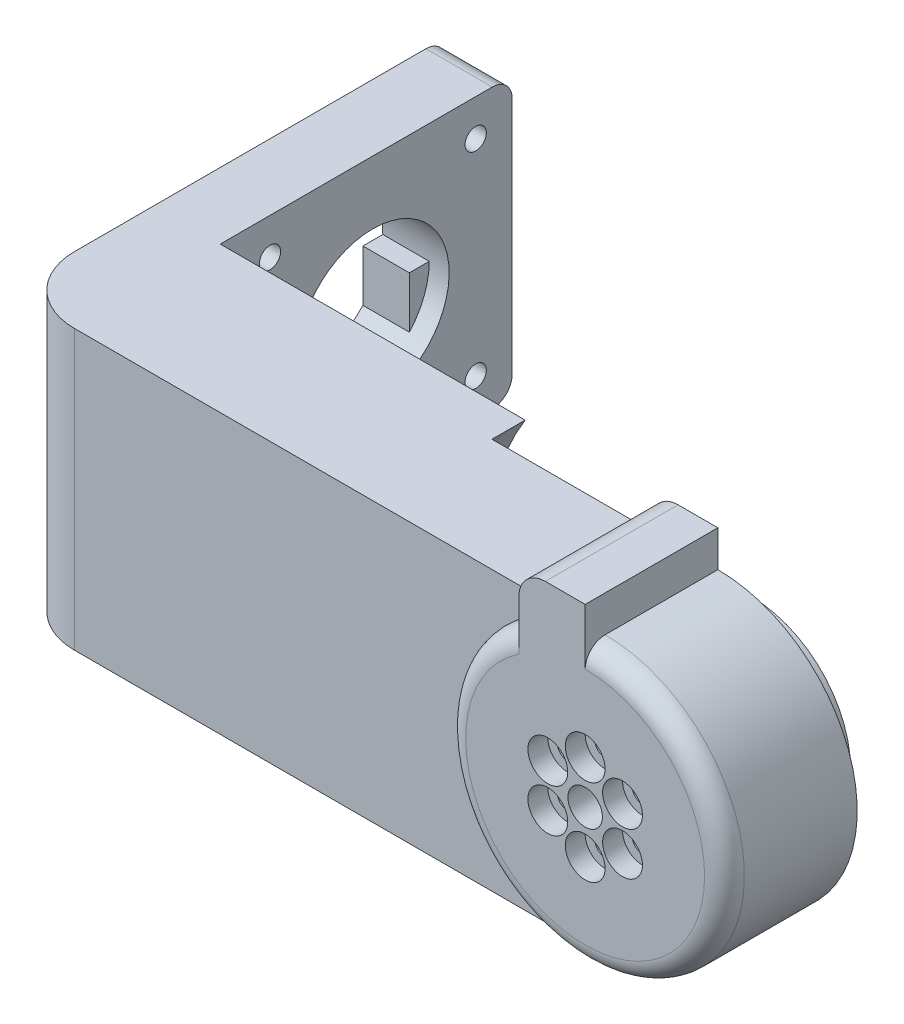
SolidWorks part; units mm, degrees
ref_plane "前视基准面" through (0, 0, 0) normal (0, 0, 1) x (1, 0, 0)
ref_plane "上视基准面" through (0, 0, 0) normal (0, 1, 0) x (1, 0, 0)
ref_plane "右视基准面" through (0, 0, 0) normal (1, 0, 0) x (0, 0, -1)
sketch "草图1" plane through (0, 0, 0) normal (0, 0, 1) x (1, 0, 0)
  line L1 (-45, 21) -> (45, 21)
  line L2 (-45, 21) -> (-45, -21)
  line L3 (-45, -21) -> (45, -21)
  line L4 (45, 21) -> (45, -21)
  line L5 (0, -21) -> (0, 21) construction
  line L6 (-45, 0) -> (45, 0) construction
  point P0 (0, 0)
  dimension "D1" = 90
  dimension "D2" = 42
extrude "凸台-拉伸1" add sketch "草图1" along normal blind 54
sketch "草图2" plane through (0, 0, 0) normal (0, 0, -1) x (-1, 0, 0)
  circle A0 centre (-45, 0) radius 21
  dimension "D1" = 42
extrude "凸台-拉伸2" add sketch "草图2" against normal up to surface (54 mm away) up to face at (0, 0, 54)
sketch "草图3" plane through (0, 0, 0) normal (0, 0, -1) x (-1, 0, 0)
  circle A0 centre (-45, 0) radius 40
  dimension "D1" = 80
extrude "切除-拉伸1" cut sketch "草图3" against normal offset from surface (49 mm away) 5 up to face at (5.25, 0, 54)
sketch "草图4" plane through (0, 0, 49) normal (0, 0, -1) x (-1, 0, 0)
  circle A0 centre (-45, 0) radius 15
  dimension "D1" = 30
extrude "凸台-拉伸3" add sketch "草图4" along normal blind 5
sketch "草图5" plane through (0, 0, 54) normal (0, 0, 1) x (1, 0, 0)
  circle A0 centre (45, 0) radius 21
  dimension "D1" = 42
extrude "凸台-拉伸4" add sketch "草图5" along normal blind 15
sketch "草图7" plane through (0, 0, 69) normal (0, 0, 1) x (1, 0, 0)
  line L0 (0, 0) -> (78.2042, 0) construction
  line L1 (45, 21) -> (45, -21) construction
  circle A0 centre (45, 0) radius 21 construction
  point P8 (45, 0)
sketch "草图10" plane through (0, 0, 0) normal (0, 0, -1) x (-1, 0, 0)
  line L0 (45, -21) -> (-10.9559, -21) construction
  line L1 (-10.9559, 21) -> (35, 21)
  line L2 (-10.9559, 21) -> (-10.9559, -21)
  line L3 (-10.9559, -21) -> (35, -21)
  line L4 (35, 21) -> (35, -21)
  line L5 (45, 21) -> (45, -21) construction
  dimension "D1" = 10
extrude "切除-拉伸2" cut sketch "草图10" against normal blind 44
sketch "草图11" plane through (0, 0, 69) normal (0, 0, 1) x (1, 0, 0)
  circle A0 centre (45, 0) radius 2.6
  circle A1 centre (45, 6.5) radius 1.55
  circle A2 centre (50.6292, 3.25) radius 1.55
  circle A3 centre (50.6292, -3.25) radius 1.55
  circle A4 centre (45, -6.5) radius 1.55
  circle A5 centre (39.3708, -3.25) radius 1.55
  circle A6 centre (39.3708, 3.25) radius 1.55
  point P17 (45, 0)
  dimension "D1" = 5.2
  dimension "D2" = 3.1
  dimension "D3" = 6.5
extrude "切除-拉伸3" cut sketch "草图11" against normal through all
sketch "草图12" plane through (0, 0, 69) normal (0, 0, 1) x (1, 0, 0)
  circle A0 centre (45, 6.5) radius 3
  circle A1 centre (50.6292, 3.25) radius 3
  circle A2 centre (50.6292, -3.25) radius 3
  circle A3 centre (45, -6.5) radius 3
  circle A4 centre (39.3708, -3.25) radius 3
  circle A5 centre (39.3708, 3.25) radius 3
  circle A6 centre (45, 0) radius 5 construction
  point P16 (45, 0)
  dimension "D1" = 6
extrude "切除-拉伸4" cut sketch "草图12" against normal blind 3
sketch "草图13" plane through (-35, 0, 0) normal (1, 0, 0) x (0, 0, -1)
  line L0 (-21, 20.3079) -> (-21, -23.4653) construction
  line L3 (-27.124, 0) -> (17.7973, 0) construction
  line L4 (-44, 21) -> (0, 21) construction
  line L5 (-44, -21) -> (0, -21) construction
  line L6 (0, -21) -> (0, 21) construction
  circle A0 centre (-21, 0) radius 11.5
  circle A1 centre (-5.5, 15.5) radius 1.6
  circle A2 centre (-5.5, -15.5) radius 1.6
  circle A3 centre (-36.5, -15.5) radius 1.6
  circle A4 centre (-36.5, 15.5) radius 1.6
  point P26 (-21, 0)
  dimension "D1" = 23
  dimension "D2" = 3.2
  dimension "D3" = 31
  dimension "D4" = 31
  dimension "D5" = 21
  dimension "D6" = 4
extrude "切除-拉伸5" cut sketch "草图13" against normal through all
fillet "圆角3" radius 3 2 edges at (-40, -21, 0) (-40, 21, 0)
sketch "草图14" plane through (-45, 0, 0) normal (-1, 0, 0) x (0, 0, 1)
  circle A0 centre (5.5, 15.5) radius 3.1
  circle A1 centre (36.5, 15.5) radius 3.1
  circle A2 centre (36.5, -15.5) radius 3.1
  circle A3 centre (5.5, -15.5) radius 3.1
  point P12 (21, 0)
  dimension "D1" = 6.2
extrude "切除-拉伸6" cut sketch "草图14" against normal blind 3
sketch "草图15" plane through (0, 0, 69) normal (0, 0, 1) x (1, 0, 0)
  line L5 (45, 21) -> (45, -21) construction
  line L6 (35, 18.4662) -> (45, 18.4662)
  line L7 (35, 18.4662) -> (35, 26.4662)
  line L8 (35, 26.4662) -> (45, 26.4662)
  line L9 (45, 18.4662) -> (45, 26.4662)
  circle A1 centre (45, 0) radius 21 construction
  dimension "D1" = 10
  dimension "D2" = 8
extrude "凸台-拉伸5" add sketch "草图15" against normal up to surface (20 mm away) up to face at (60, 0, 49)
fillet "圆角6" radius 3 1 edges at (50.158, -20.3567, 69)
fillet "圆角8" radius 4 1 edges at (35, 26.4662, 59)
sketch "草图16" plane through (0, 0, 54) normal (0, 0, 1) x (1, 0, 0)
  line L0 (-45, -21) -> (45, -21) construction
  line L1 (35, 21) -> (35, 18.4662) construction
  line L2 (35, 21) -> (-45, 21) construction
  line L3 (-45, -21) -> (45, -21)
  line L4 (35, 21) -> (35, 18.4662)
  line L5 (35, 21) -> (-45, 21)
  line L6 (-45, 21) -> (-45, -21) construction
  line L7 (-45, 21) -> (-45, -21)
  arc A0 (35, 18.4662) -> (45, -21) centre (45, 0) ccw construction
  arc A1 (35, 18.4662) -> (45, -21) centre (45, 0) ccw
extrude "凸台-拉伸6" add sketch "草图16" along normal blind 12
fillet "圆角9" radius 10 1 edges at (-45, 0, 66)
sketch "草图17" plane through (-45, 0, 0) normal (-1, 0, 0) x (0, 0, 1)
  line L0 (27.124, 0) -> (-17.7973, 0) construction
  line L1 (9.5, 0) -> (12.5, 0)
  line L2 (9.5, 0) -> (9.5, -7.746)
  line L3 (9.5, -7.746) -> (12.5, -7.746)
  line L4 (12.5, 0) -> (12.5, -7.746)
  circle A0 centre (21, 0) radius 11.5 construction
  circle A1 centre (21, 0) radius 11.5 construction
  dimension "D1" = 3
extrude "凸台-拉伸7" add sketch "草图17" against normal blind 7
